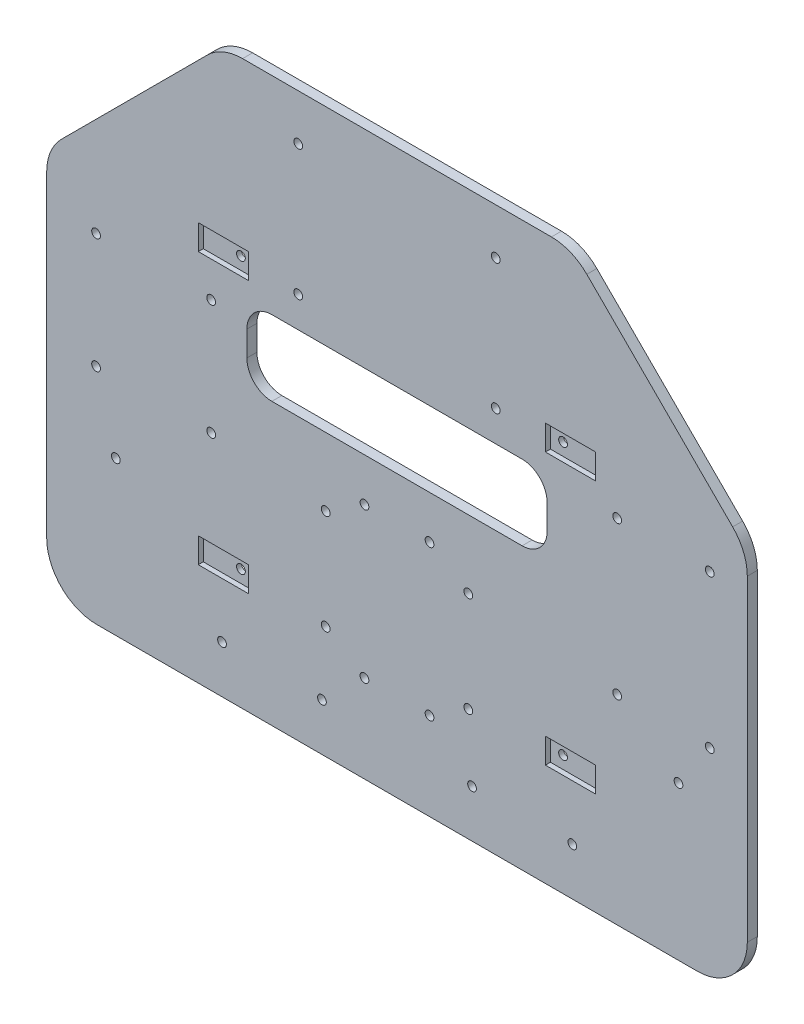
SolidWorks part; units mm, degrees
ref_plane "前视基准面" through (0, 0, 0) normal (0, 0, 1) x (1, 0, 0)
ref_plane "上视基准面" through (0, 0, 0) normal (0, 1, 0) x (1, 0, 0)
ref_plane "右视基准面" through (0, 0, 0) normal (1, 0, 0) x (0, 0, -1)
sketch "草图3" plane through (0, 0, 0) normal (0, 0, 1) x (1, 0, 0)
  line L1 (73.5057, 259.0895) -> (196.9372, 259.0895)
  line L2 (-4.7785, 180.8052) -> (-4.7785, 54.0895)
  line L3 (15.2215, 34.0895) -> (255.2215, 34.0895)
  line L4 (275.2215, 180.8052) -> (275.2215, 54.0895)
  line L6 (1.0793, 194.9474) -> (59.3636, 253.2316)
  line L9 (211.0793, 253.2316) -> (269.3636, 194.9474)
  arc A0 (73.5057, 259.0895) -> (59.3636, 253.2316) centre (73.5057, 239.0895) ccw
  arc A1 (211.0793, 253.2316) -> (196.9372, 259.0895) centre (196.9372, 239.0895) ccw
  arc A2 (1.0793, 194.9474) -> (-4.7785, 180.8052) centre (15.2215, 180.8052) ccw
  arc A3 (-4.7785, 54.0895) -> (15.2215, 34.0895) centre (15.2215, 54.0895) ccw
  arc A4 (255.2215, 34.0895) -> (275.2215, 54.0895) centre (255.2215, 54.0895) ccw
  arc A5 (275.2215, 180.8052) -> (269.3636, 194.9474) centre (255.2215, 180.8052) ccw
  dimension "D1" = 20
  dimension "D2" = 20
  dimension "D3" = 20
extrude "凸台-拉伸1" add sketch "草图3" along normal blind 4
ref_plane "基准面1" through (0, 0, 4) normal (0, 0, 1) x (1, 0, 0)
sketch "草图4" plane through (0, 0, 4) normal (0, 0, 1) x (1, 0, 0)
  line L0 (135.2215, 259.0895) -> (135.2215, 34.0895) construction
  line L1 (135.2215, 240.7454) -> (174.6915, 240.7454) construction
  line L2 (154.9565, 240.7454) -> (154.9565, 188.6354) construction
  line L4 (135.2215, 188.6354) -> (154.9565, 188.6354) construction
  line L6 (154.9565, 214.6904) -> (187.4334, 214.6904) construction
  line L10 (196.9372, 259.0895) -> (73.5057, 259.0895) construction
  line L11 (15.2215, 34.0895) -> (255.2215, 34.0895) construction
  line L13 (135.2215, 53.0683) -> (165.2215, 53.0683) construction
  circle A5 centre (174.6915, 240.7454) radius 1.75
  circle A14 centre (174.6915, 188.6354) radius 1.75
  circle A15 centre (95.7515, 188.6354) radius 1.75
  circle A16 centre (95.7515, 240.7454) radius 1.75
  circle A17 centre (165.2215, 53.0683) radius 1.75
  circle A18 centre (105.2215, 53.0683) radius 1.75
sketch "草图6" plane through (0, 0, 4) normal (0, 0, 1) x (1, 0, 0)
  line L0 (135.2215, 265.6507) -> (135.2215, 27.2875) construction
  circle A0 centre (223.2215, 174.8801) radius 1.75
  circle A1 centre (260.2215, 174.8801) radius 1.75
  circle A2 centre (260.2215, 113.8801) radius 1.75
  circle A3 centre (223.2215, 113.8801) radius 1.75
extrude "切除-拉伸3" cut sketch "草图6" against normal blind 4
extrude "切除-拉伸4" cut sketch "草图4" against normal blind 4
sketch "草图7" plane through (0, 0, 4) normal (0, 0, 1) x (1, 0, 0)
  circle A0 centre (122.2215, 129.0895) radius 1.75
  circle A1 centre (148.2215, 129.0895) radius 1.75
  circle A2 centre (122.2215, 69.0895) radius 1.75
  circle A3 centre (148.2215, 69.0895) radius 1.75
extrude "切除-拉伸5" cut sketch "草图7" against normal blind 4
sketch "草图8" plane through (0, 0, 4) normal (0, 0, 1) x (1, 0, 0)
  circle A0 centre (22.8673, 95.4947) radius 1.75
  circle A1 centre (65.2937, 53.0683) radius 1.75
  circle A2 centre (247.7201, 95.4947) radius 1.75
  circle A3 centre (205.2937, 53.0683) radius 1.75
extrude "切除-拉伸6" cut sketch "草图8" against normal blind 4
sketch "草图9" plane through (0, 0, 4) normal (0, 0, 1) x (1, 0, 0)
  line L2 (135.2215, 176.3247) -> (85.2215, 176.3247)
  line L3 (75.2215, 166.3247) -> (75.2215, 156.3247)
  line L4 (85.2215, 146.3247) -> (185.2215, 146.3247)
  line L5 (195.2215, 156.3247) -> (195.2215, 166.3247)
  line L6 (185.2215, 176.3247) -> (135.2215, 176.3247)
  arc A0 (185.2215, 176.3247) -> (195.2215, 166.3247) centre (185.2215, 166.3247) cw
  arc A1 (195.2215, 156.3247) -> (185.2215, 146.3247) centre (185.2215, 156.3247) cw
  arc A2 (85.2215, 146.3247) -> (75.2215, 156.3247) centre (85.2215, 156.3247) cw
  arc A3 (85.2215, 176.3247) -> (75.2215, 166.3247) centre (85.2215, 166.3247) ccw
  dimension "D1" = 10
extrude "切除-拉伸7" cut sketch "草图9" against normal blind 4
sketch "草图10" plane through (0, 0, 4) normal (0, 0, 1) x (1, 0, 0)
  line L0 (135.2215, 259.0895) -> (135.2215, 34.0895) construction
  line L1 (196.9372, 259.0895) -> (73.5057, 259.0895) construction
  line L2 (15.2215, 34.0895) -> (255.2215, 34.0895) construction
  line L3 (106.7215, 79.0895) -> (106.7215, 119.0895) construction
  line L4 (106.7215, 119.0895) -> (163.7215, 119.0895) construction
  line L5 (163.7215, 119.0895) -> (163.7215, 79.0895) construction
  line L6 (163.7215, 79.0895) -> (106.7215, 79.0895) construction
  circle A2 centre (106.7215, 79.0895) radius 1.75
  circle A3 centre (163.7215, 79.0895) radius 1.75
  circle A4 centre (106.7215, 119.0895) radius 1.75
  circle A5 centre (163.7215, 119.0895) radius 1.75
extrude "切除-拉伸9" cut sketch "草图10" against normal blind 4
sketch "草图11" plane through (0, 0, 4) normal (0, 0, 1) x (1, 0, 0)
  line L0 (-3.2561, 188.4589) -> (273.6991, 188.4589) construction
  line L1 (65.8521, 257.5671) -> (65.8521, 34.0895) construction
  line L2 (15.2215, 34.0895) -> (255.2215, 34.0895) construction
  line L3 (204.5909, 131.2717) -> (65.8521, 131.2717) construction
  line L4 (-4.7785, 54.0895) -> (275.2215, 54.0895) construction
  line L5 (135.2215, 259.0895) -> (135.2215, 34.0895) construction
  line L6 (55.7944, 193.4754) -> (75.9097, 193.4754)
  line L7 (55.7944, 193.4754) -> (55.7944, 183.4424)
  line L8 (55.7944, 183.4424) -> (75.9097, 183.4424)
  line L9 (75.9097, 193.4754) -> (75.9097, 183.4424)
  line L10 (55.7944, 193.4754) -> (75.9097, 183.4424) construction
  line L11 (55.7944, 183.4424) -> (75.9097, 193.4754) construction
  line L12 (196.9372, 259.0895) -> (73.5057, 259.0895) construction
  line L13 (204.5909, 188.4589) -> (204.5909, 74.0846) construction
  line L14 (55.7944, 85.1011) -> (75.9097, 85.1011)
  line L15 (75.9097, 75.0681) -> (75.9097, 85.1011)
  line L16 (55.7944, 75.0681) -> (75.9097, 75.0681)
  line L17 (55.7944, 75.0681) -> (55.7944, 85.1011)
  line L18 (214.6485, 183.4424) -> (194.5332, 183.4424)
  line L19 (194.5332, 193.4754) -> (194.5332, 183.4424)
  line L20 (214.6485, 193.4754) -> (194.5332, 193.4754)
  line L21 (214.6485, 193.4754) -> (214.6485, 183.4424)
  line L22 (214.6485, 75.0681) -> (214.6485, 85.1011)
  line L23 (214.6485, 75.0681) -> (194.5332, 75.0681)
  line L24 (194.5332, 75.0681) -> (194.5332, 85.1011)
  line L25 (214.6485, 85.1011) -> (194.5332, 85.1011)
  arc A0 (1.0793, 194.9474) -> (-4.7785, 180.8052) centre (15.2215, 180.8052) ccw construction
  arc A1 (275.2215, 180.8052) -> (269.3636, 194.9474) centre (255.2215, 180.8052) ccw construction
  arc A2 (73.5057, 259.0895) -> (59.3636, 253.2316) centre (73.5057, 239.0895) ccw construction
  circle A8 centre (70.8521, 188.4589) radius 1.75
  circle A12 centre (70.8521, 80.0846) radius 1.75
  circle A13 centre (199.5909, 80.0846) radius 1.75
  circle A14 centre (199.5909, 188.4589) radius 1.75
  point P26 (65.8521, 188.4589)
  point P49 (0, 0)
  point P50 (0, 0)
  point P51 (0, 0)
extrude "切除-拉伸10" cut sketch "草图11" against normal blind 2 contours L9 L6 L7 L8 A8 | L17 L16 L15 L14 A12 | L22 L25 L24 L23 A13 | L21 L20 L19 L18 A14 region at (65.6018, 188.4589, 4) region at (65.6018, 80.0846, 4) region at (204.8412, 188.4589, 4) region at (204.8412, 80.0846, 4)
extrude "切除-拉伸11" cut sketch "草图11<5>" against normal blind 10 contours A12 | A13 | A14 | A8 region at (70.8521, 188.4589, 4) region at (70.8521, 80.0846, 4) region at (199.5909, 80.0846, 4) region at (199.5909, 188.4589, 4)
sketch "草图11<5>" plane through (0, 0, 4) normal (0, 0, 1) x (1, 0, 0) same geometry as "草图11"
ref_plane "基准面2" through (0, 0, 4) normal (0, 0, 1) x (1, 0, 0)
sketch "草图12" plane through (0, 0, 4) normal (0, 0, 1) x (1, 0, 0)
  line L0 (11.9614, 172.3122) -> (11.9614, 165.6511) construction
  line L1 (11.9614, 172.3122) -> (63.9614, 172.3122)
  line L2 (11.9614, 172.3122) -> (11.9614, 120.3122)
  line L3 (11.9614, 120.3122) -> (63.9614, 120.3122)
  line L4 (63.9614, 172.3122) -> (63.9614, 120.3122)
  line L5 (11.9614, 172.3122) -> (63.9614, 120.3122) construction
  line L6 (11.9614, 120.3122) -> (63.9614, 172.3122) construction
  line L7 (11.9614, 172.3122) -> (11.9614, 166.5784) construction
  line L8 (11.9614, 166.5784) -> (11.9614, 164.5784) construction
  line L9 (63.9614, 172.3122) -> (63.9614, 169.3122) construction
  line L10 (63.9614, 169.3122) -> (60.9614, 169.3122) construction
  circle A0 centre (60.9614, 169.3122) radius 1.75
  circle A1 centre (60.9614, 123.3122) radius 1.75
  circle A2 centre (14.9614, 123.3122) radius 1.75
  circle A3 centre (14.9614, 169.3122) radius 1.75
  point P0 (37.9614, 146.3122)
  point P20 (37.9614, 146.3122)
  dimension "D1" = 4
extrude "切除-拉伸13" cut sketch "草图12" against normal through all contours A3 | A2 | A1 | A0
